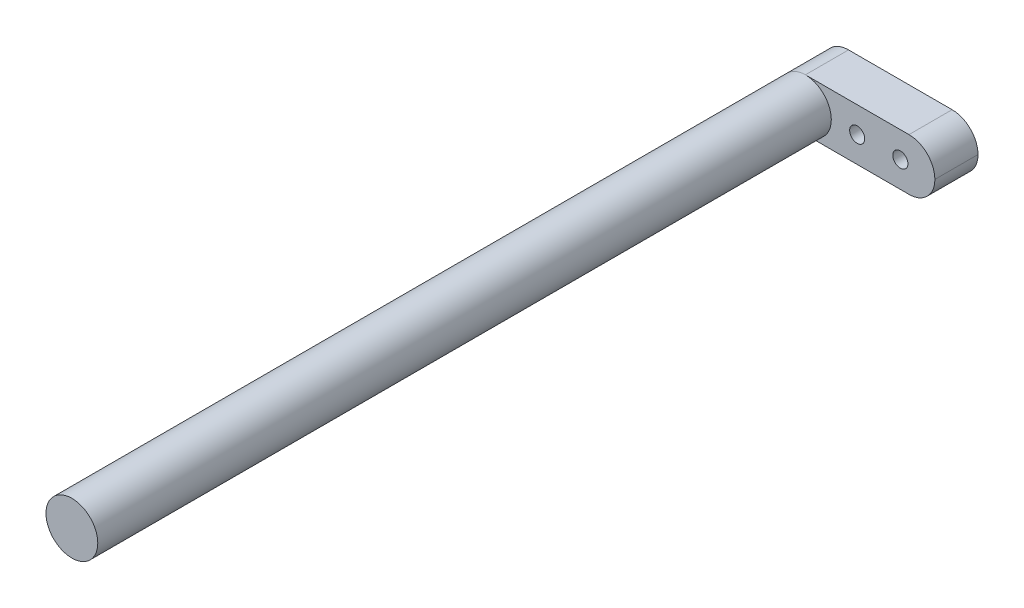
SolidWorks part; units mm, degrees
ref_plane "Front Plane" through (0, 0, 0) normal (0, 0, 1) x (1, 0, 0)
ref_plane "Top Plane" through (0, 0, 0) normal (0, 1, 0) x (1, 0, 0)
ref_plane "Right Plane" through (0, 0, 0) normal (1, 0, 0) x (0, 0, -1)
sketch "Sketch1" plane through (0, 0, 0) normal (0, 0, 1) x (1, 0, 0)
  line L5 (5, 6) -> (-31, 6)
  line L6 (5, 6) -> (5, -6)
  line L7 (5, -6) -> (-31, -6)
  line L8 (-31, 6) -> (-31, -6)
  dimension "D1" = 12
  dimension "D2" = 6
  dimension "D3" = 31
  dimension "D4" = 5
extrude "Boss-Extrude1" add sketch "Sketch1" along normal blind 10
sketch "Sketch2" plane through (0, 0, 10) normal (0, 0, 1) x (1, 0, 0)
  circle A0 centre (-25, 0) radius 6
  dimension "D3" = 12
  dimension "D1" = 25
extrude "Boss-Extrude2" add sketch "Sketch2" along normal blind 170
sketch "Sketch6" plane through (0, 0, 0) normal (0, 1, 0) x (1, 0, 0)
  line L0 (-31, -180) -> (-19, -180) construction
  circle A0 centre (-25, -175) radius 1.75
  dimension "D2" = 3.5
  dimension "D1" = 5
sketch "Sketch7" plane through (0, 0, 0) normal (0, 0, -1) x (-1, 0, 0)
  line L0 (31, 6) -> (31, -6) construction
  circle A0 centre (3, 0) radius 1.75
  circle A1 centre (13, 0) radius 1.75
  dimension "D1" = 3.5
  dimension "D2" = 10
  dimension "D3" = 18
extrude "Cut-Extrude4" cut sketch "Sketch7" against normal up to next
fillet "Fillet1" radius 6 4 edges at (5, -6, 5) (5, 6, 5) (-31, -6, 5) (-31, 6, 5)
